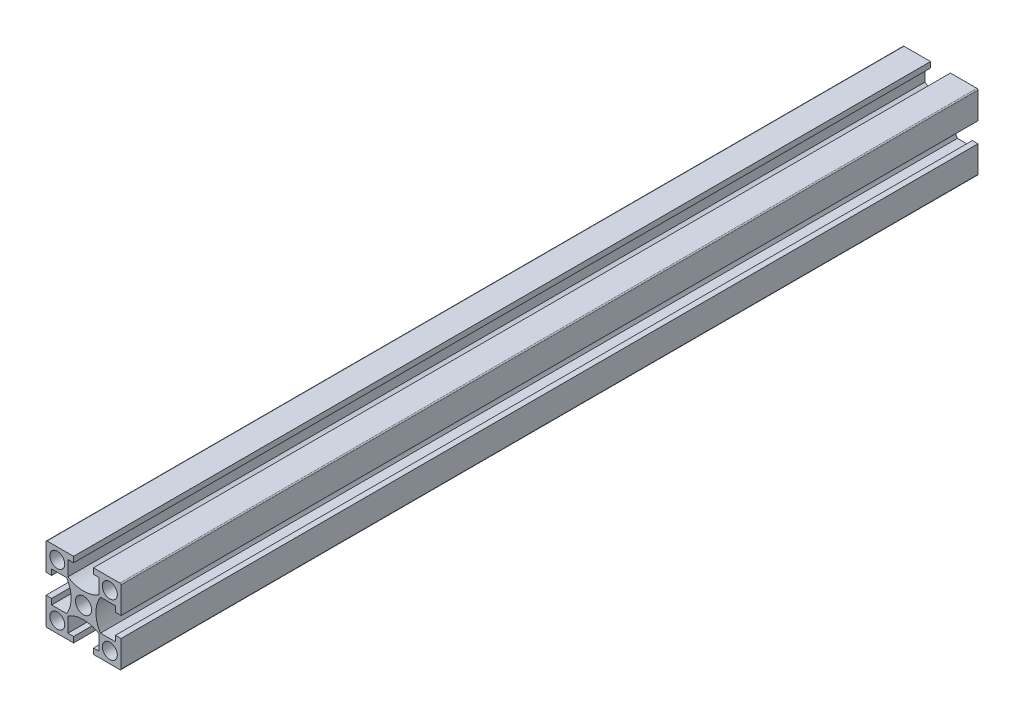
SolidWorks part; units mm, degrees
material "3.0255 (EN-AW 1350A)"
ref_plane "정면" through (0, 0, 0) normal (0, 0, 1) x (1, 0, 0)
ref_plane "윗면" through (0, 0, 0) normal (0, 1, 0) x (1, 0, 0)
ref_plane "우측면" through (0, 0, 0) normal (1, 0, 0) x (0, 0, -1)
sketch "스케치1" plane through (0, 0, 0) normal (0, 0, 1) x (1, 0, 0)
  line L0 (0, 32.0265) -> (0, -31.6588) construction
  line L1 (-10, 10) -> (-10, -10)
  line L2 (-10, 10) -> (10, 10)
  line L3 (-10, 2.65) -> (-8.5, 2.65)
  line L4 (13.6618, 0) -> (-11.6993, 0) construction
  line L5 (-8.5, 2.65) -> (-8.5, 4.15)
  line L6 (-8.5, 4.15) -> (-4.5032, 4.15)
  line L7 (-10, -2.65) -> (-8.5, -2.65)
  line L8 (-8.5, -2.65) -> (-8.5, -4.15)
  line L9 (-8.5, -4.15) -> (-4.5032, -4.15)
  line L10 (-10, -10) -> (10, -10)
  line L11 (10, 10) -> (10, -10)
  circle A0 centre (-7, 7) radius 2
  circle A1 centre (-7, -7) radius 2
  arc A2 (-4.5032, 4.15) -> (-4.5032, -4.15) centre (-11.0587, 0) cw
  circle A3 centre (0, 0) radius 2.15
  circle A4 centre (7, 7) radius 2
  circle A5 centre (7, -7) radius 2
  point P21 (-10, 0)
  point P23 (-3.3, 0)
  point P31 (0, -10)
  point P32 (0, 10)
  dimension "D3" = 4
  dimension "D9" = 6.7
  dimension "D10" = 4.3
  dimension "D11" = 7.7587
  dimension "D1" = 20
  dimension "D2" = 20
  dimension "D4" = 14
  dimension "D5" = 14
  dimension "D6" = 5.3
  dimension "D7" = 8.3
  dimension "D8" = 1.5
extrude "보스-돌출1" add sketch "스케치1" along normal blind 345 contours A0 | A4 | A3 | A5 | A1 | A2 L6 L5 L3 L1 L7 L8 L9 | L2 L11 L10 L1 region at (-6.6069, 0, 0) region at (-7, 7, 0) region at (-7, -7, 0) region at (0, 0, 0) region at (7, 7, 0) region at (7, -7, 0)
extrude "컷-돌출1" cut sketch "스케치1<3>" along normal up to next contours A2 L6 L5 L3 L1 L7 L8 L9 region at (-6.6069, 0, 0)
sketch "스케치1<3>" plane through (0, 0, 0) normal (0, 0, 1) x (1, 0, 0) same geometry as "스케치1"
pattern_circular "원형 패턴1" count 4 over 360 about axis through (0, 0, 345) along (0, 0, -1) of "컷-돌출1" reverse direction yes
fillet "필렛1" radius 0.3 4 edges at (10, -10, 172.5) (-10, -10, 172.5) (-10, 10, 172.5) (10, 10, 172.5)
sketch "스케치2" plane through (0, 0, 0) normal (1, 0, 0) x (0, 0, -1)
  circle A0 centre (-25, 0) radius 2.5
  dimension "D1" = 5
  dimension "D2" = 25
extrude "컷-돌출2" cut sketch "스케치2" against normal through all both and the other way through all
sketch "스케치4" plane through (0, 10, 0) normal (0, 1, 0) x (1, 0, 0)
  line L0 (0, -11) -> (0, 11) construction
  line L1 (2.65, -345) -> (9.7, -345) construction
  line L3 (-2.65, -106.62) -> (2.65, -106.62) construction
  line L4 (-2.65, -345) -> (-2.65, 0) construction
  line L5 (2.65, -345) -> (2.65, 0) construction
  line L6 (2.65, 0) -> (9.7, 0) construction
  circle A4 centre (0, -303) radius 2.15
  dimension "D3" = 106.62
  dimension "D5" = 42
extrude "컷-돌출3" cut sketch "스케치4" against normal through all
sketch "스케치6" plane through (0, 10, 0) normal (0, 1, 0) x (1, 0, 0)
  line L0 (0, -11) -> (0, 11) construction
  line L1 (4.15, 0) -> (-4.15, 0) construction
  line L3 (-9.7, 0) -> (-2.65, 0) construction
  circle A0 centre (0, -236.9) radius 2.15
  circle A1 centre (0, -184.9) radius 2.15
  circle A2 centre (0, -10.15) radius 1.9797
  circle A3 centre (0, -62.15) radius 2.15
  dimension "D1" = 184.9
  dimension "D2" = 236.9
  dimension "D4" = 52
  dimension "D3" = 10.15
extrude "컷-돌출4" cut sketch "스케치6" against normal through all
sketch "스케치7" plane through (0, 10, 0) normal (0, 1, 0) x (1, 0, 0)
  line L0 (-10, -116.62) -> (10, -116.62)
  line L1 (-10, -345) -> (-10, 0) construction
  line L2 (10, 0) -> (10, -345) construction
  line L6 (-10, -116.62) -> (-10, 0)
  line L7 (-10, 0) -> (10, 0)
  line L8 (10, 0) -> (10, -116.62)
extrude "컷-돌출5" cut sketch "스케치7" against normal through all
